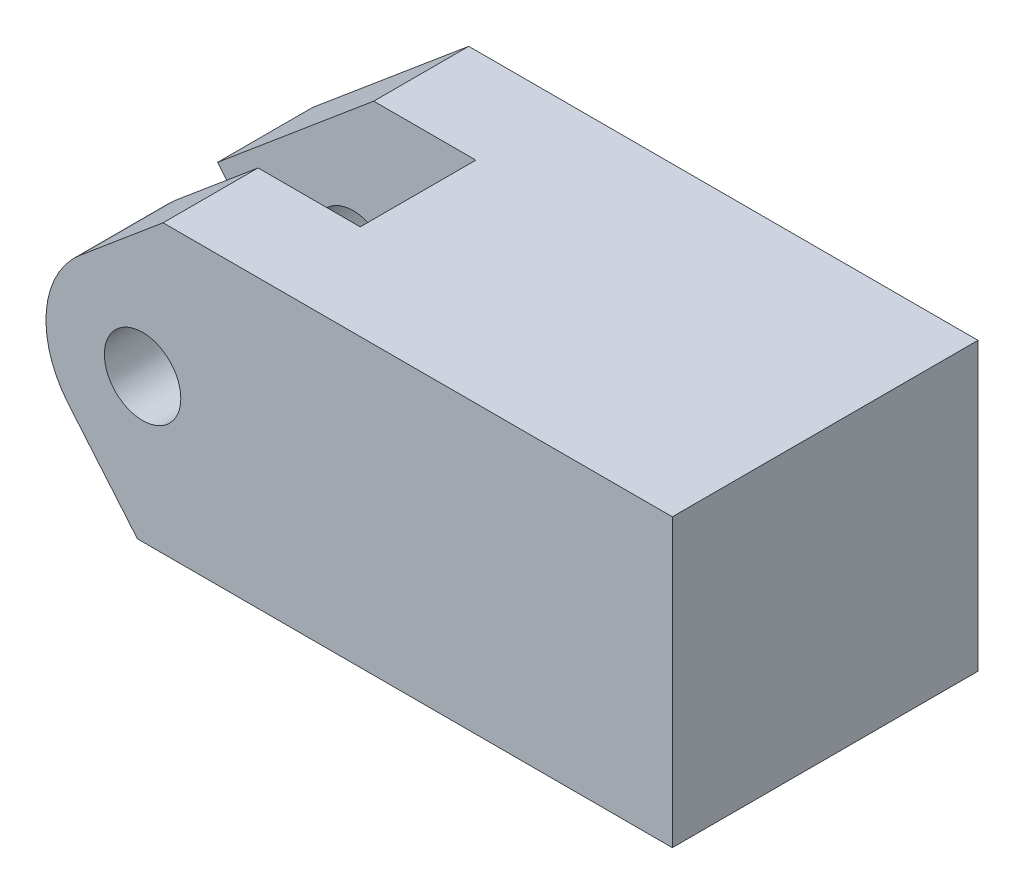
SolidWorks part; units mm, degrees
ref_plane "Спереди" through (0, 0, 0) normal (0, 0, 1) x (1, 0, 0)
ref_plane "Сверху" through (0, 0, 0) normal (0, 1, 0) x (1, 0, 0)
ref_plane "Справа" through (0, 0, 0) normal (1, 0, 0) x (0, 0, -1)
sketch "Эскиз1" plane through (0, 0, 0) normal (0, 1, 0) x (1, 0, 0)
  line L1 (-17.5, 8) -> (17.5, 8)
  line L2 (-17.5, 8) -> (-17.5, -8)
  line L3 (-17.5, -8) -> (17.5, -8)
  line L4 (17.5, 8) -> (17.5, -8)
  line L5 (-17.5, 8) -> (17.5, -8) construction
  line L6 (-17.5, -8) -> (17.5, 8) construction
  point P0 (0, 0)
extrude "Вытянуть1" add sketch "Эскиз1" along normal blind 15
sketch "Эскиз2" plane through (0, 15, 0) normal (0, 1, 0) x (1, 0, 0)
  line L0 (0, 0) -> (24.4698, 0) construction
  line L1 (-17.5, 8) -> (-17.5, -8) construction
  line L2 (-31.1885, 3.0269) -> (-3.8115, 3.0269)
  line L3 (-31.1885, 3.0269) -> (-31.1885, -3.0269)
  line L4 (-31.1885, -3.0269) -> (-3.8115, -3.0269)
  line L5 (-3.8115, 3.0269) -> (-3.8115, -3.0269)
  line L6 (-31.1885, 3.0269) -> (-3.8115, -3.0269) construction
  line L7 (-31.1885, -3.0269) -> (-3.8115, 3.0269) construction
  point P1 (-17.5, 0)
extrude "Вытянуть2" cut sketch "Эскиз2" against normal through all
sketch "Эскиз3" plane through (0, 0, 8) normal (0, 0, 1) x (1, 0, 0)
  line L0 (-17.5, 7.5) -> (-21.2397, 7.5) construction
  circle A0 centre (-10.2298, 7.5) radius 2
extrude "Вытянуть3" cut sketch "Эскиз3" against normal through all
chamfer "Фаска1" distance 7 angle 50 4 edges at (-17.5, 0, -5.5134) (-17.5, 0, 5.5134) (-17.5, 15, 5.5134) (-17.5, 15, -5.5134)
fillet "Скругление1" radius 5 1 edges at (-17.3315, 8.1414, 5.5134)
